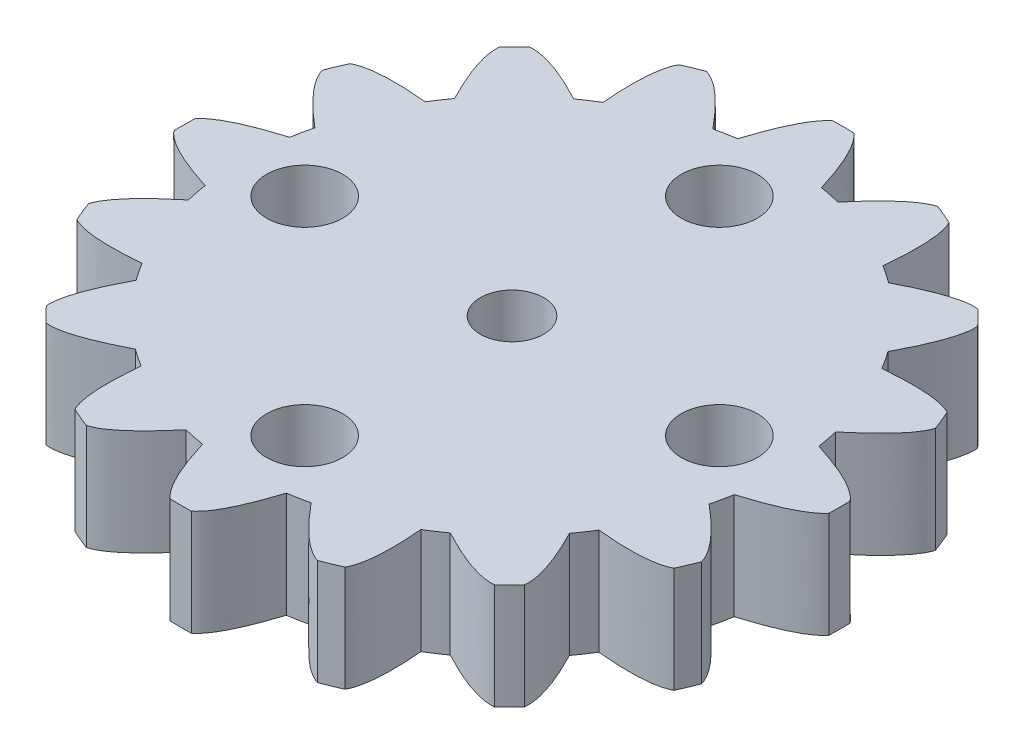
SolidWorks part; units mm, degrees
material "ABS"
ref_plane "Front Plane" through (0, 0, 0) normal (0, 0, 1) x (1, 0, 0)
ref_plane "Top Plane" through (0, 0, 0) normal (0, 1, 0) x (1, 0, 0)
ref_plane "Right Plane" through (0, 0, 0) normal (1, 0, 0) x (0, 0, -1)
sketch "Sketch1" plane through (0, 0, 0) normal (0, 1, 0) x (1, 0, 0)
  line L0 (7.543, 10.2575) -> (10.3436, 7.4246) construction
  line L2 (8.9433, 8.8411) -> (11.0767, 10.9502) construction
  line L3 (11.0767, 10.9502) -> (11.2141, 11.086)
  circle A0 centre (0, 0) radius 12.7324
  circle A1 centre (0, 0) radius 15.5756
  spline S0 degree 2 poles (10.3436, 7.4246) (13.485, 13.3309) (7.543, 10.2575) knots 0 0 0 1 1 1
  point P3 (7.543, 10.2575)
  point P4 (10.3436, 7.4246)
  point P6 (10.7195, 11.3001)
  point P12 (6.7149, 10.8177)
  point P14 (11.2141, 11.086)
  point P15 (11.4226, 10.5889)
  point P16 (5.382, 11.539)
  dimension "D1" = 25.4648
  dimension "D4" = 3
  dimension "D5" = 1
  dimension "D2" = 4
  dimension "D3" = 1
extrude "Boss-Extrude4" add sketch "Sketch1" along normal blind 5 contours A0 | A0 S0 A1 region at (9.8762, 0, -9.7634) region at (0, 0, 0)
pattern_circular "CirPattern6" count 16 every 22.5 about axis through (0, 5, 0) along (0, 1, 0) of "Boss-Extrude4"
sketch "Sketch2" plane through (0, 5, 0) normal (0, 1, 0) x (1, 0, 0)
  circle A0 centre (0, 0) radius 1.5
  circle A1 centre (9.8, 0) radius 1.8
  dimension "D1" = 3
  dimension "D2" = 3.6
extrude "Cut-Extrude1" cut sketch "Sketch2" against normal blind 10 contours A0 region at (0, 5, 0)
sketch "Sketch3" plane through (0, 0, 0) normal (0, -1, 0) x (1, 0, 0)
sketch "Sketch5" plane through (0, 5, 0) normal (0, 1, 0) x (1, 0, 0)
  circle A1 centre (9.8, 0) radius 1.8
  dimension "D1" = 3.6
extrude "Cut-Extrude2" cut sketch "Sketch5" against normal blind 10
pattern_circular "CirPattern7" count 4 over 360 about axis through (0, 5, 0) along (0, 1, 0) of "Cut-Extrude2"
equation "\"number-of-teeth\"= 16"
equation "\"gear-size\"= 4mm"
equation "\"circumference\"= \"number-of-teeth\" * ( ( 1 + \"space-between-teeth\" ) * \"gear-size\" )"
equation "\"space-between-teeth\"= .25"
equation "\"D1@Sketch1\" = \"circumference\" / pi"
equation "\"D2@Sketch1\"=\"gear-size\""
equation "\"gear-length\"= 3mm"
equation "\"D4@Sketch1\"=\"gear-length\""
equation "\"D5@Sketch1\"=\"gear-size\" * \"space-between-teeth\""
equation "\"D3@Sketch1\"=\"gear-size\" * \"space-between-teeth\""
equation "\"D1@CirPattern6\"=\"number-of-teeth\""
equation "\"D2@CirPattern6\"=360 / \"number-of-teeth\""
